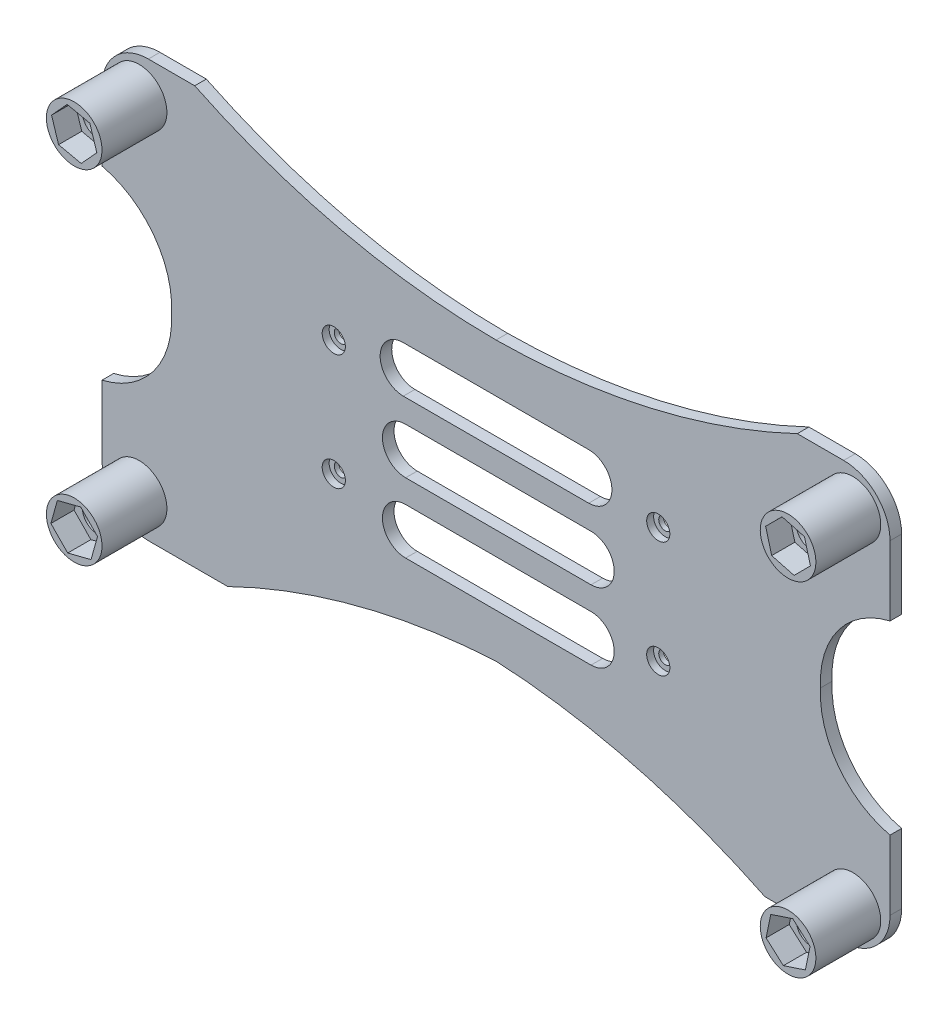
SolidWorks part; units mm, degrees
ref_plane "前视基准面" through (0, 0, 0) normal (0, 0, 1) x (1, 0, 0)
ref_plane "上视基准面" through (0, 0, 0) normal (0, 1, 0) x (1, 0, 0)
ref_plane "右视基准面" through (0, 0, 0) normal (1, 0, 0) x (0, 0, -1)
sketch "草图1" plane through (0, 0, 0) normal (0, 0, 1) x (1, 0, 0)
  line L1 (-72.5741, 45.4874) -> (77.4259, 45.4874)
  line L2 (-82.5741, 35.4874) -> (-82.5741, -34.5126)
  line L3 (-72.5741, -44.5126) -> (77.4259, -44.5126)
  line L4 (87.4259, 35.4874) -> (87.4259, -34.5126)
  arc A0 (-72.5741, 45.4874) -> (-82.5741, 35.4874) centre (-72.5741, 35.4874) ccw
  arc A1 (-72.5741, -44.5126) -> (-82.5741, -34.5126) centre (-72.5741, -34.5126) cw
  arc A2 (87.4259, 35.4874) -> (77.4259, 45.4874) centre (77.4259, 35.4874) ccw
  arc A3 (87.4259, -34.5126) -> (77.4259, -44.5126) centre (77.4259, -34.5126) cw
  dimension "D1" = 10
  dimension "D2" = 10
  dimension "D3" = 10
  dimension "D4" = 10
  dimension "D5" = 90
  dimension "D6" = 170
extrude "凸台-拉伸1" add sketch "草图1" along normal blind 2.5
ref_plane "for screw hole" through (0, 0, 2.5) normal (0, 0, 1) x (1, 0, 0)
sketch "草图2" plane through (0, 0, 2.5) normal (0, 0, 1) x (1, 0, 0)
  line L0 (77.4259, 45.4874) -> (-72.5741, 45.4874) construction
  line L1 (-82.5741, 35.4874) -> (-82.5741, -34.5126) construction
  line L2 (-72.5741, -44.5126) -> (77.4259, -44.5126) construction
  line L3 (87.4259, -34.5126) -> (87.4259, 35.4874) construction
  line L4 (-55.4572, -44.5126) -> (60.4378, -44.5126)
  line L5 (-62.5741, 45.4874) -> (67.4259, 45.4874)
  line L6 (87.4259, 20.4874) -> (87.4259, -19.5126)
  line L7 (-82.5741, 20.4874) -> (-82.5741, -19.5126)
  line L8 (-17.5741, 15) -> (22.4259, 15) construction
  line L9 (-17.5741, 20) -> (22.4259, 20)
  line L10 (-17.5741, 10) -> (22.4259, 10)
  line L11 (-17.0794, 0) -> (22.9206, 0) construction
  line L12 (-17.0794, 5) -> (22.9206, 5)
  line L13 (-17.0794, -5) -> (22.9206, -5)
  line L14 (-17.0794, -15) -> (22.9206, -15) construction
  line L15 (-17.0794, -10) -> (22.9206, -10)
  line L16 (-17.0794, -20) -> (22.9206, -20)
  circle A0 centre (-32.5741, 12.9874) radius 1.4
  circle A1 centre (-32.5741, -12.0126) radius 1.4
  circle A2 centre (37.4259, 12.9874) radius 1.4
  circle A3 centre (37.4259, -12.0126) radius 1.4
  arc A4 (67.4259, 45.4874) -> (2.4259, 30.4874) centre (1.0956, 184.5854) cw
  arc A5 (-62.5741, 45.4874) -> (2.4259, 30.4874) centre (2.8104, 180.4869) ccw
  arc A6 (-55.4572, -44.5126) -> (2.4259, -29.5126) centre (10.3578, -179.3027) cw
  arc A7 (60.4378, -44.5126) -> (2.4259, -29.5126) centre (-5.3618, -179.3103) ccw
  arc A8 (87.4259, 20.4874) -> (72.4259, 0.4874) centre (91.8434, 1.5492) ccw
  arc A9 (87.4259, -19.5126) -> (72.4259, 0.4874) centre (91.8434, -0.5745) cw
  arc A10 (-82.5741, 20.4874) -> (-67.5741, 0.4874) centre (-86.9917, 1.5492) cw
  arc A11 (-82.5741, -19.5126) -> (-67.5741, 0.4874) centre (-86.9917, -0.5745) ccw
  arc A12 (-17.5741, 20) -> (-17.5741, 10) centre (-17.5741, 15) ccw
  arc A13 (22.4259, 10) -> (22.4259, 20) centre (22.4259, 15) ccw
  arc A14 (-17.0794, 5) -> (-17.0794, -5) centre (-17.0794, 0) ccw
  arc A15 (22.9206, -5) -> (22.9206, 5) centre (22.9206, 0) ccw
  arc A16 (-17.0794, -10) -> (-17.0794, -20) centre (-17.0794, -15) ccw
  arc A17 (22.9206, -20) -> (22.9206, -10) centre (22.9206, -15) ccw
  point P12 (2.4259, 30.4874)
  point P13 (2.4259, -29.5126)
  point P16 (-62.5741, 45.4874)
  point P17 (67.4259, 45.4874)
  point P18 (-55.4572, -44.5126)
  point P19 (60.4378, -44.5126)
  point P29 (-67.5741, 0.4874)
  point P33 (72.4259, 0.4874)
  point P34 (-82.5741, 20.4874)
  point P35 (-82.5741, -19.5126)
  point P36 (87.4259, -19.5126)
  point P37 (87.4259, 20.4874)
  point P49 (0, 0)
  point P50 (0, 0)
  point P54 (2.4259, 15)
  point P59 (0, 0)
  point P61 (2.9206, 0)
  point P68 (2.9206, -15)
  dimension "D2" = 2.8
  dimension "D3" = 2.8
  dimension "D4" = 2.8
  dimension "D8" = 32.5
  dimension "D9" = 50
  dimension "D10" = 50
  dimension "D11" = 2.8
  dimension "D21" = 45
  dimension "D29" = 15
  dimension "D5" = 70
  dimension "D6" = 70
  dimension "D7" = 25
  dimension "D12" = 25
  dimension "D13" = 32.5
  dimension "D14" = 85
  dimension "D15" = 15
  dimension "D16" = 85
  dimension "D17" = 15
  dimension "D18" = 20
  dimension "D19" = 20
  dimension "D20" = 26.9881
  dimension "D22" = 15
  dimension "D23" = 15
  dimension "D24" = 45
  dimension "D25" = 25
  dimension "D26" = 25
  dimension "D27" = 25
  dimension "D28" = 25
  dimension "D30" = 15
  dimension "D31" = 15
extrude "切除-拉伸1" cut sketch "草图2" against normal blind 10 and the other way blind 42
ref_plane "for outer screw hole" through (0, 0, 2.5) normal (0, 0, 1) x (1, 0, 0)
sketch "草图3" plane through (0, 0, 2.5) normal (0, 0, 1) x (1, 0, 0)
  circle A0 centre (-32.5741, 12.9874) radius 2.5
  circle A1 centre (37.4259, 12.9874) radius 2.5
  circle A2 centre (37.4259, -12.0126) radius 2.5
  circle A3 centre (-32.5741, -12.0126) radius 2.5
  dimension "D1" = 5
  dimension "D2" = 5
  dimension "D3" = 5
  dimension "D4" = 5
extrude "切除-拉伸2" cut sketch "草图3" against normal blind 1.5
ref_plane "for stands" through (0, 0, 2.5) normal (0, 0, 1) x (1, 0, 0)
sketch "草图7" plane through (0, 0, 2.5) normal (0, 0, 1) x (1, 0, 0)
  line L0 (77.4259, 45.4874) -> (67.4259, 45.4874) construction
  line L1 (-82.5741, 35.4874) -> (-82.5741, 20.4874) construction
  line L2 (-72.5741, -44.5126) -> (-55.4572, -44.5126) construction
  line L3 (87.4259, -34.5126) -> (87.4259, -19.5126) construction
  circle A0 centre (-74.5741, 37.4874) radius 6
  circle A1 centre (-74.5741, -36.5126) radius 6
  circle A2 centre (79.4259, 37.4874) radius 6
  circle A3 centre (79.4259, -36.5126) radius 6
  point P12 (79.4259, -30.5126)
  point P14 (79.4259, 31.4874)
  dimension "D1" = 12
  dimension "D2" = 12
  dimension "D3" = 12
  dimension "D4" = 12
  dimension "D7" = 8
  dimension "D5" = 8
  dimension "D6" = 8
  dimension "D8" = 8
  dimension "D9" = 8
  dimension "D10" = 8
  dimension "D11" = 8
  dimension "D12" = 8
extrude "凸台-拉伸4" add sketch "草图7" along normal blind 14
ref_plane "button left hole" through (0, 0, 16.5) normal (0, 0, 1) x (1, 0, 0)
ref_plane "up left hole" through (0, 0, 16.5) normal (0, 0, 1) x (1, 0, 0)
ref_plane "up right hole" through (0, 0, 16.5) normal (0, 0, 1) x (1, 0, 0)
ref_plane "button right hole" through (0, 0, 16.5) normal (0, 0, 1) x (1, 0, 0)
sketch "草图9" plane through (0, 0, 16.5) normal (0, 0, 1) x (1, 0, 0)
  line L1 (-70.9446, -40.2262) -> (-69.5433, -35.2262)
  line L2 (-69.5433, -35.2262) -> (-73.1728, -31.5126)
  line L3 (-73.1728, -31.5126) -> (-78.2036, -32.7991)
  line L4 (-78.2036, -32.7991) -> (-79.6049, -37.7991)
  line L5 (-79.6049, -37.7991) -> (-75.9754, -41.5126)
  line L6 (-75.9754, -41.5126) -> (-70.9446, -40.2262)
  circle A0 centre (-74.5741, -36.5126) radius 4.497 construction
  circle A1 centre (-74.5741, -36.5126) radius 6 construction
  dimension "D1" = 5
  dimension "D2" = 0
extrude "button left nut " cut sketch "草图9" against normal blind 5
sketch "草图10" plane through (0, 0, 16.5) normal (0, 0, 1) x (1, 0, 0)
  line L1 (-73.0607, 32.7219) -> (-69.6904, 36.4153)
  line L2 (-69.6904, 36.4153) -> (-71.2038, 41.1808)
  line L3 (-71.2038, 41.1808) -> (-76.0876, 42.2528)
  line L4 (-76.0876, 42.2528) -> (-79.4578, 38.5594)
  line L5 (-79.4578, 38.5594) -> (-77.9444, 33.794)
  line L6 (-77.9444, 33.794) -> (-73.0607, 32.7219)
  circle A0 centre (-74.5741, 37.4874) radius 4.3301 construction
  circle A1 centre (-74.5741, 37.4874) radius 6 construction
  dimension "D1" = 5
  dimension "D2" = 0
extrude "up left nut" cut sketch "草图10" against normal blind 5
sketch "草图11" plane through (0, 0, 16.5) normal (0, 0, 1) x (1, 0, 0)
  line L1 (80.729, 32.6602) -> (84.2579, 36.2023)
  line L2 (84.2579, 36.2023) -> (82.9548, 41.0295)
  line L3 (82.9548, 41.0295) -> (78.1228, 42.3146)
  line L4 (78.1228, 42.3146) -> (74.5938, 38.7724)
  line L5 (74.5938, 38.7724) -> (75.897, 33.9452)
  line L6 (75.897, 33.9452) -> (80.729, 32.6602)
  circle A0 centre (79.4259, 37.4874) radius 4.3301 construction
  circle A2 centre (79.4259, 37.4874) radius 6 construction
  dimension "D2" = 0
  dimension "D1" = 5
extrude "up right nut" cut sketch "草图11" against normal blind 5
sketch "草图12" plane through (0, 0, 16.5) normal (0, 0, 1) x (1, 0, 0)
  line L1 (83.1629, -39.8344) -> (84.1712, -34.9371)
  line L2 (84.1712, -34.9371) -> (80.4341, -31.6153)
  line L3 (80.4341, -31.6153) -> (75.6888, -33.1908)
  line L4 (75.6888, -33.1908) -> (74.6806, -38.0881)
  line L5 (74.6806, -38.0881) -> (78.4176, -41.4099)
  line L6 (78.4176, -41.4099) -> (83.1629, -39.8344)
  circle A0 centre (79.4259, -36.5126) radius 4.3301 construction
  circle A1 centre (79.4259, -36.5126) radius 6 construction
  dimension "D2" = 0
  dimension "D1" = 5
extrude "button right nut" cut sketch "草图12" against normal blind 5
ref_plane "基准面13" through (0, 0, 16.5) normal (0, 0, 1) x (1, 0, 0)
ref_plane "基准面14" through (0, 0, 16.5) normal (0, 0, 1) x (1, 0, 0)
ref_plane "基准面15" through (0, 0, 16.5) normal (0, 0, 1) x (1, 0, 0)
ref_plane "基准面16" through (0, 0, 16.5) normal (0, 0, 1) x (1, 0, 0)
sketch "草图13" plane through (0, 0, 16.5) normal (0, 0, 1) x (1, 0, 0)
  circle A0 centre (-74.5741, -36.5126) radius 3.25
  dimension "D1" = 6.5
extrude "切除-拉伸7" cut sketch "草图13" against normal blind 13
sketch "草图15" plane through (0, 0, 16.5) normal (0, 0, 1) x (1, 0, 0)
  circle A0 centre (-74.5741, 37.4874) radius 3.25
  circle A1 centre (-74.5741, 37.4874) radius 6 construction
  dimension "D1" = 6.5
  dimension "D2" = 0
extrude "切除-拉伸8" cut sketch "草图15" against normal blind 13
sketch "草图16" plane through (0, 0, 16.5) normal (0, 0, 1) x (1, 0, 0)
  circle A0 centre (79.4259, 37.4874) radius 3.25
  dimension "D1" = 6.5
extrude "切除-拉伸9" cut sketch "草图16" against normal blind 13
sketch "草图17" plane through (0, 0, 16.5) normal (0, 0, 1) x (1, 0, 0)
  circle A0 centre (79.4259, -36.5126) radius 3.25
  circle A1 centre (79.4259, -36.5126) radius 6 construction
  point P4 (79.4259, -36.2982)
  point P5 (79.4259, -36.2982)
  point P6 (79.4259, -36.2982)
  point P7 (79.4259, -36.2982)
  dimension "D1" = 6.5
  dimension "D2" = 0
extrude "切除-拉伸10" cut sketch "草图17" against normal blind 13
